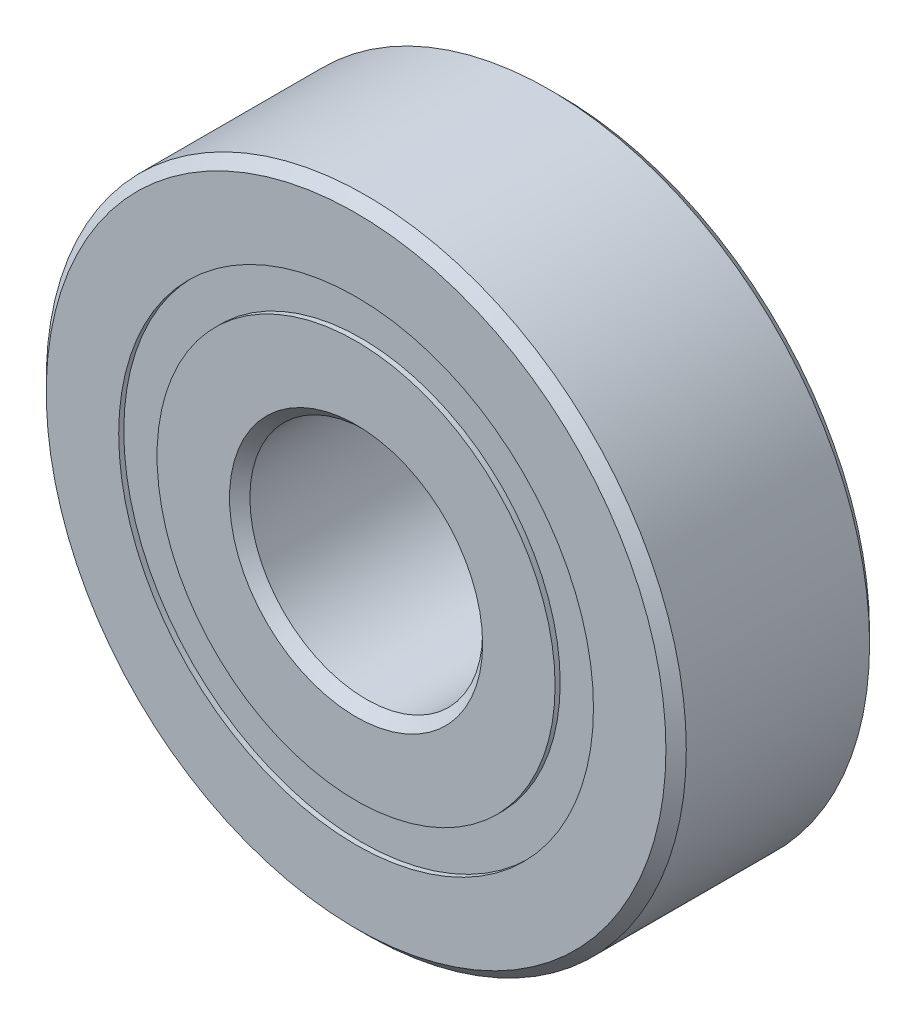
SolidWorks part; units mm, degrees
material "AISI 316 Annealed Stainless Steel Bar (SS)"
ref_plane "Front Plane" through (0, 0, 0) normal (0, 0, 1) x (1, 0, 0)
ref_plane "Top Plane" through (0, 0, 0) normal (0, 1, 0) x (1, 0, 0)
ref_plane "Right Plane" through (0, 0, 0) normal (1, 0, 0) x (0, 0, -1)
sketch "Sketch1" plane through (0, 0, 0) normal (1, 0, 0) x (0, 0, -1)
  line L0 (-3.5, 0) -> (3.5, 0) construction
  line L1 (0, 11) -> (0, -11) construction
  line L2 (3.15, 11) -> (-3.15, 11)
  line L3 (-3.15, 11) -> (-3.5, 10.65)
  line L4 (-3.5, 10.65) -> (-3.5, 8.1593)
  line L5 (-3.5, 8.1593) -> (-1.5556, 8.1593)
  line L6 (3.5, 8.1593) -> (1.5556, 8.1593)
  line L7 (3.5, 10.65) -> (3.5, 8.1593)
  line L8 (3.15, 11) -> (3.5, 10.65)
  line L9 (0, 11) -> (0, 7.5) construction
  line L10 (0, 7.5) -> (0, 4) construction
  arc A0 (-1.5556, 8.1593) -> (1.5556, 8.1593) centre (0, 7.5) cw
  point P14 (0, 4)
  dimension "D3" = 3.1111
  dimension "D1" = 45
  dimension "Width" = 7
  dimension "OD" = 22
  dimension "D2" = 0.35
  dimension "Shaft Dia" = 8
  dimension "D4" = 0.6593
revolve "Revolve1" add sketch "Sketch1" angle 360 about L0
sketch "Sketch3" plane through (0, 0, 0) normal (1, 0, 0) x (0, 0, -1)
  line L0 (-3.5, 6.8407) -> (-1.5556, 6.8407)
  line L1 (0, 11) -> (0, -11) construction
  line L2 (-3.5, 10.65) -> (-3.5, 8.1593) construction
  line L3 (-3.5, 6.8407) -> (-3.5, 4.35)
  line L4 (-3.15, 11) -> (-3.5, 10.65) construction
  line L5 (-3.5, 4.35) -> (-3.15, 4)
  line L6 (-3.15, 4) -> (3.15, 4)
  line L7 (3.15, 11) -> (3.15, -11) construction
  line L8 (3.15, 4) -> (3.5, 4.35)
  line L9 (3.5, -10.65) -> (3.5, 10.65) construction
  line L10 (3.5, 4.35) -> (3.5, 6.8407)
  line L11 (3.5, 6.8407) -> (1.5556, 6.8407)
  line L13 (3.15, 11) -> (3.5, 10.65) construction
  arc A0 (1.5556, 8.1593) -> (-1.5556, 8.1593) centre (0, 7.5) ccw construction
  arc A1 (1.5556, 6.8407) -> (-1.5556, 6.8407) centre (0, 7.5) cw
revolve "Revolve3" add sketch "Sketch3" angle 360 about L0
sketch "Sketch4" plane through (0, 0, 0) normal (1, 0, 0) x (0, 0, -1)
  line L0 (-1.6895, 7.5) -> (1.6895, 7.5)
  arc A2 (-1.6895, 7.5) -> (1.6895, 7.5) centre (0, 7.5) cw
  arc A3 (1.5556, 8.1593) -> (-1.5556, 8.1593) centre (0, 7.5) ccw construction
revolve "Revolve4" add sketch "Sketch4" angle 360 about L0
ref_axis "Axis1" through (0, 0, -3.5) along (0, 0, 1)
pattern_circular "CirPattern1" count 10 every 36 about axis through (0, 0, -3.5) along (0, 0, 1) of bodies 104
sketch "Sketch6" plane through (0, 0, 0) normal (1, 0, 0) x (0, 0, -1)
  line L0 (-3.5, 8.1593) -> (-1.5556, 8.1593) construction
  line L1 (-3.325, 8.1593) -> (-1.6895, 8.1593)
  line L2 (-3.325, 8.1593) -> (-3.325, 6.8407)
  line L3 (-3.325, 6.8407) -> (-1.6895, 6.8407)
  line L4 (-1.6895, 8.1593) -> (-1.6895, 6.8407)
  line L5 (-3.5, 6.8407) -> (-1.5556, 6.8407) construction
  line L6 (3.5, 8.1593) -> (1.5556, 8.1593) construction
  line L7 (3.325, 8.1593) -> (1.6895, 8.1593)
  line L8 (3.325, 8.1593) -> (3.325, 6.8407)
  line L9 (3.325, 6.8407) -> (1.6895, 6.8407)
  line L10 (1.6895, 8.1593) -> (1.6895, 6.8407)
  line L11 (3.5, 6.8407) -> (1.5556, 6.8407) construction
  line L12 (-3.15, 11) -> (-3.5, 10.65) construction
  point P18 (-3.325, 10.825)
revolve "Revolve5" add sketch "Sketch6" angle 360 about L0
equation "\"D2@Sketch1\" = \"Width@Sketch1\"*.05"
equation "\"D3@Sketch1\" = \"Width@Sketch1\"/2.25"
equation "\"D4@Sketch1\" = (((\"OD@Sketch1\"-\"Width@Sketch1\")/2)/3.25)/3.5"
equation "\"D2@CirPattern1\" = 360/\"Balls@CirPattern1\""
